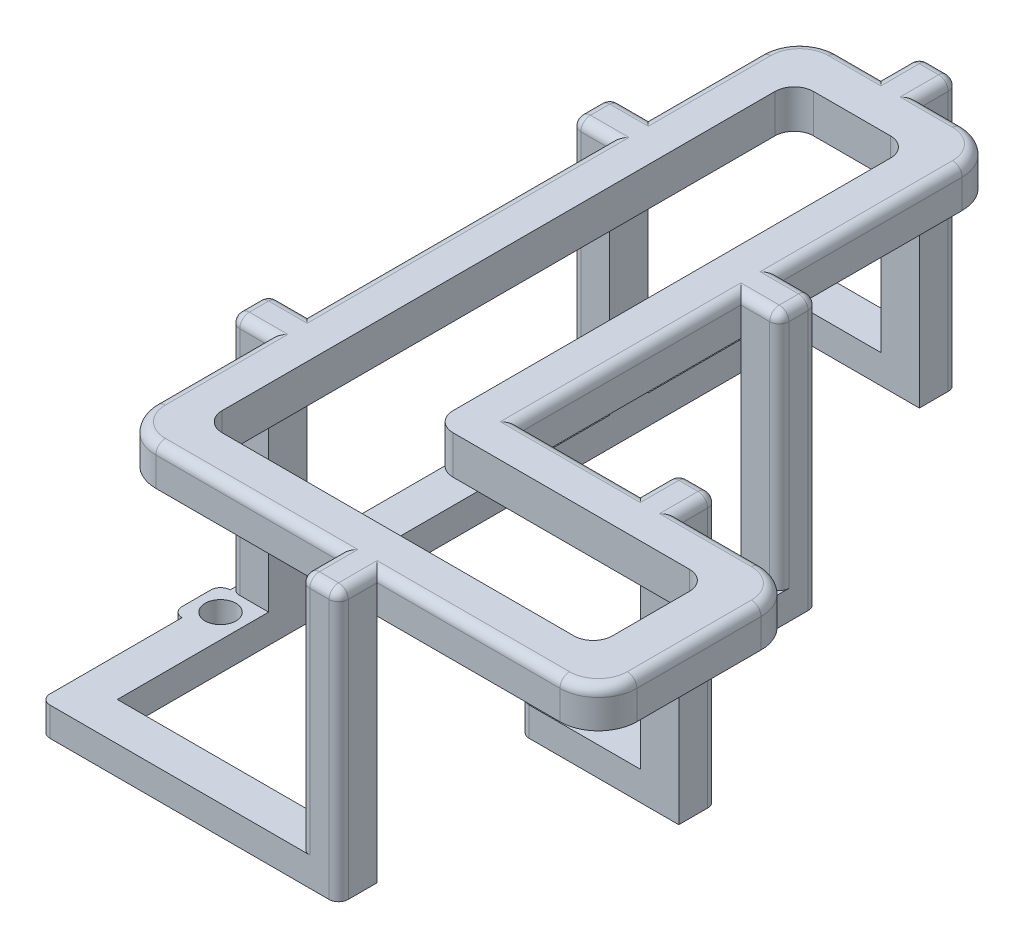
SolidWorks part; units mm, degrees
ref_plane "Front Plane" through (0, 0, 0) normal (0, 0, 1) x (1, 0, 0)
ref_plane "Top Plane" through (0, 0, 0) normal (0, 1, 0) x (1, 0, 0)
ref_plane "Right Plane" through (0, 0, 0) normal (1, 0, 0) x (0, 0, -1)
sketch "Sketch1" plane through (0, 0, 0) normal (0, 1, 0) x (1, 0, 0)
  line L0 (0, 0) -> (23, 0)
  line L1 (0, 0) -> (0, 15.725)
  line L3 (0, 70.9) -> (8.45, 70.9)
  line L4 (20.9, 70.9) -> (20.9, 47.9)
  line L5 (20.9, 20.9) -> (33.45, 20.9)
  line L6 (20.9, 43.9) -> (20.9, 20.9)
  line L7 (10.45, 74.9) -> (12.45, 74.9)
  line L8 (12.45, 74.9) -> (12.45, 70.9)
  line L9 (10.45, 74.9) -> (8.45, 74.9)
  line L10 (8.45, 74.9) -> (8.45, 70.9)
  line L11 (50, 0) -> (50, 20.9)
  line L12 (0, 70.9) -> (0, 55.175)
  line L13 (12.45, 70.9) -> (20.9, 70.9)
  line L14 (-4, 53.175) -> (-4, 55.175)
  line L15 (-4, 55.175) -> (0, 55.175)
  line L16 (-4, 53.175) -> (-4, 51.175)
  line L17 (-4, 51.175) -> (0, 51.175)
  line L18 (0, 51.175) -> (0, 35.45)
  line L19 (-4, 17.725) -> (-4, 19.725)
  line L20 (-4, 19.725) -> (0, 19.725)
  line L21 (-4, 17.725) -> (-4, 15.725)
  line L22 (-4, 15.725) -> (0, 15.725)
  line L23 (27, 0) -> (50, 0)
  line L24 (24.9, 45.9) -> (24.9, 47.9)
  line L25 (24.9, 47.9) -> (20.9, 47.9)
  line L26 (24.9, 45.9) -> (24.9, 43.9)
  line L27 (24.9, 43.9) -> (20.9, 43.9)
  line L29 (25, -4) -> (27, -4)
  line L30 (27, -4) -> (27, 0)
  line L31 (25, -4) -> (23, -4)
  line L32 (23, -4) -> (23, 0)
  line L33 (37.45, 20.9) -> (50, 20.9)
  line L39 (35.45, 24.9) -> (37.45, 24.9)
  line L40 (37.45, 24.9) -> (37.45, 20.9)
  line L41 (35.45, 24.9) -> (33.45, 24.9)
  line L42 (33.45, 24.9) -> (33.45, 20.9)
  line L43 (0, 19.725) -> (0, 35.45)
extrude "Boss-Extrude1" add sketch "Sketch1" along normal blind 4
sketch "Sketch2" plane through (0, 0, 0) normal (0, -1, 0) x (1, 0, 0)
  line L0 (27, 0) -> (23, 0)
  line L1 (23, 0) -> (23, 4)
  line L2 (23, 4) -> (27, 4)
  line L3 (27, 4) -> (27, 0)
  line L4 (33.45, -20.9) -> (37.45, -20.9)
  line L5 (37.45, -20.9) -> (37.45, -24.9)
  line L6 (37.45, -24.9) -> (33.45, -24.9)
  line L7 (33.45, -24.9) -> (33.45, -20.9)
  line L8 (20.9, -43.9) -> (20.9, -47.9)
  line L9 (20.9, -47.9) -> (24.9, -47.9)
  line L10 (24.9, -47.9) -> (24.9, -43.9)
  line L11 (24.9, -43.9) -> (20.9, -43.9)
  line L12 (0, -15.725) -> (0, -19.725)
  line L13 (0, -19.725) -> (-4, -19.725)
  line L14 (-4, -19.725) -> (-4, -15.725)
  line L15 (-4, -15.725) -> (0, -15.725)
  line L16 (0, -51.175) -> (0, -55.175)
  line L17 (0, -55.175) -> (-4, -55.175)
  line L18 (-4, -55.175) -> (-4, -51.175)
  line L19 (-4, -51.175) -> (0, -51.175)
  line L20 (12.45, -74.9) -> (12.45, -70.9)
  line L21 (12.45, -70.9) -> (8.45, -70.9)
  line L22 (8.45, -70.9) -> (8.45, -74.9)
  line L23 (8.45, -74.9) -> (12.45, -74.9)
extrude "Boss-Extrude2" add sketch "Sketch2" along normal blind 24
fillet "Fillet2" radius 4 5 edges at (20.9, 2, -70.9) (0, 2, -70.9) (0, 2, 0) (50, 2, 0) (50, 2, -20.9)
sketch "Sketch5" plane through (0, -24, 0) normal (0, -1, 0) x (-1, 0, 0)
  line L0 (0, 19.725) -> (0, 0)
  line L1 (-27, -4) -> (4, -4)
  line L2 (-27, 0) -> (0, 0)
  line L3 (4, 51.175) -> (4, -4)
  line L4 (4, 51.175) -> (4, 74.9)
  line L5 (-12.45, 74.9) -> (4, 74.9)
  line L6 (-12.45, 70.9) -> (0, 70.9)
  line L7 (0, 19.725) -> (0, 70.9)
  line L8 (-27, -4) -> (-27, 0)
  line L9 (-12.45, 70.9) -> (-12.45, 74.9)
extrude "Boss-Extrude3" add sketch "Sketch5" against normal blind 3
sketch "Sketch7" plane through (0, -24, 0) normal (0, -1, 0) x (1, 0, 0)
  line L0 (24.9, -47.9) -> (24.9, -34.9)
  line L1 (37.45, -24.9) -> (33.45, -24.9)
  line L4 (37.45, -20.9) -> (37.45, -24.9)
  line L5 (20.9, -47.9) -> (24.9, -47.9)
  line L12 (20.9, -20.9) -> (20.9, -47.9)
  line L13 (20.9, -20.9) -> (37.45, -20.9)
  line L17 (28.9, -24.9) -> (28.9, -28.9)
  line L18 (28.9, -28.9) -> (24.9, -28.9)
  line L19 (28.9, -24.9) -> (33.45, -24.9)
  line L20 (24.9, -28.9) -> (24.9, -34.9)
  circle A0 centre (24.9, -24.9) radius 1.6
extrude "Boss-Extrude4" add sketch "Sketch7" against normal blind 3
sketch "Sketch8" plane through (0, -21, 0) normal (0, 1, 0) x (1, 0, 0)
  line L0 (0, 15.725) -> (-5, 15.725)
  line L1 (-5, 15.725) -> (-5, 10.725)
  line L2 (-5, 10.725) -> (0, 10.725)
  line L3 (0, 15.725) -> (0, 0) construction
  line L4 (0, 10.725) -> (0, 15.725)
  line L5 (0, 55.175) -> (0, 60.175)
  line L6 (0, 66.9) -> (0, 55.175) construction
  line L7 (0, 60.175) -> (-5, 60.175)
  line L8 (0, 55.175) -> (-5, 55.175)
  line L9 (-5, 55.175) -> (-5, 60.175)
extrude "Boss-Extrude5" add sketch "Sketch8" against normal blind 3
sketch "Sketch9" plane through (0, -21, 0) normal (0, 1, 0) x (1, 0, 0)
  circle A2 centre (-2.5, 57.675) radius 1.6
  circle A3 centre (-2.5, 13.225) radius 1.6
extrude "Cut-Extrude1" cut sketch "Sketch9" against normal blind 3
fillet "Fillet3" radius 1 21 edges at (8.45, -8.5, -74.9) (12.45, -10, -74.9) (33.45, -8.5, -24.9) (28.9, -22.5, -24.9) (28.9, -22.5, -28.9) (24.9, -22.5, -28.9) (24.9, -8.5, -43.9) (24.9, -10, -47.9) (37.45, -10, -24.9) (27, -10, 4) (23, -8.5, 4) (-4, -22.5, 4) (-4, -22.5, -74.9) (-4, -8.5, -55.175) (-4, -8.5, -51.175) (-4, -8.5, -19.725) (-4, -8.5, -15.725) (-5, -22.5, -15.725) (-5, -22.5, -10.725) (-5, -22.5, -60.175) (-5, -22.5, -55.175)
fillet "Fillet4" radius 1 47 edges at (12.1571, 4, -74.6071) (12.45, 4, -72.4) (14.675, 4, -70.9) (19.7284, 4, -69.7284) (20.9, 4, -57.4) (22.4, 4, -47.9) (24.6071, 4, -47.6071) (24.9, 4, -45.9) (24.6071, 4, -44.1929) (22.4, 4, -43.9) (20.9, 4, -32.4) (27.175, 4, -20.9) (33.45, 4, -22.4) (33.7429, 4, -24.6071) (35.45, 4, -24.9) (37.1571, 4, -24.6071) (37.45, 4, -22.4) (41.725, 4, -20.9) (48.8284, 4, -19.7284) (50, 4, -10.45) (48.8284, 4, -1.1716) (36.5, 4, 0) (27, 4, 1.5) (26.7071, 4, 3.7071) (25, 4, 4) (23.2929, 4, 3.7071) (23, 4, 1.5) (13.5, 4, 0) (1.1716, 4, -1.1716) (0, 4, -9.8625) (-1.5, 4, -15.725) (-3.7071, 4, -16.0179) (-4, 4, -17.725) (-3.7071, 4, -19.4321) (-1.5, 4, -19.725) (0, 4, -35.45) (-1.5, 4, -51.175) (-3.7071, 4, -51.4679) (-4, 4, -53.175) (-3.7071, 4, -54.8821) (-1.5, 4, -55.175) (0, 4, -61.0375) (1.1716, 4, -69.7284) (6.225, 4, -70.9) (8.45, 4, -72.4) (8.7429, 4, -74.6071) (10.45, 4, -74.9)
sketch "Sketch10" plane through (0, 4, 0) normal (0, 1, 0) x (1, 0, 0)
  line L4 (10.45, 65.9) -> (16.45, 65.9)
  line L5 (10.45, 65.9) -> (4.45, 65.9)
  line L6 (4.45, 65.9) -> (4.45, 4.45)
  line L7 (45, 10.45) -> (45, 4.45)
  line L8 (45, 4.45) -> (4.45, 4.45)
  line L9 (16.45, 65.9) -> (16.45, 16.45)
  line L10 (45, 10.45) -> (45, 16.45)
  line L11 (45, 16.45) -> (16.45, 16.45)
extrude "Cut-Extrude2" cut sketch "Sketch10" against normal blind 6
fillet "Fillet5" radius 2 6 edges at (16.45, 2, -16.45) (45, 2, -4.45) (45, 2, -16.45) (4.45, 2, -4.45) (4.45, 2, -65.9) (16.45, 2, -65.9)
fillet "Fillet6" radius 1 1 edges at (20.9, -22.5, -20.9)
